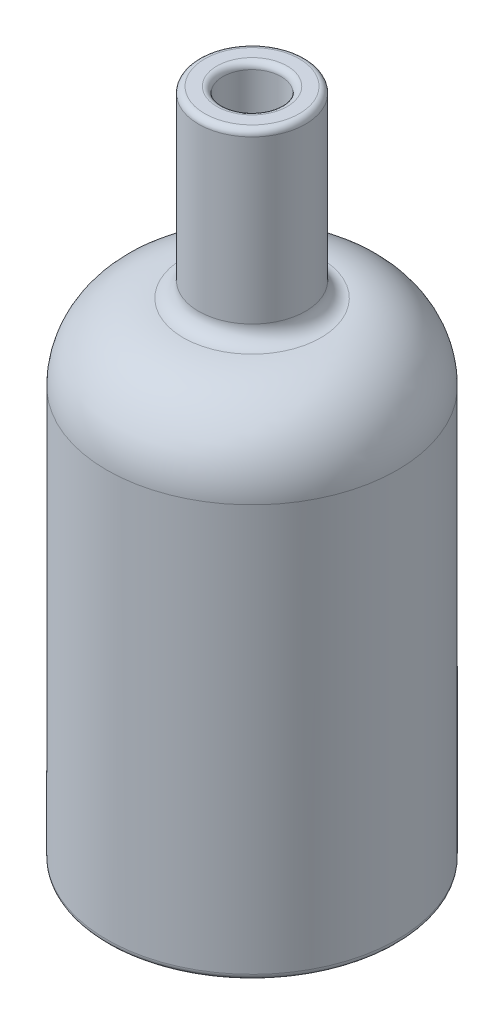
SolidWorks part; units mm, degrees
ref_plane "Front Plane" through (0, 0, 0) normal (0, 0, 1) x (1, 0, 0)
ref_plane "Top Plane" through (0, 0, 0) normal (0, 1, 0) x (1, 0, 0)
ref_plane "Right Plane" through (0, 0, 0) normal (1, 0, 0) x (0, 0, -1)
sketch "Sketch2" plane through (0, 0, 0) normal (0, 0, 1) x (1, 0, 0)
  line L0 (0, 0) -> (0, 75.6247) construction
  line L1 (0, 0) -> (47.5, 0)
  line L2 (47.5, 0) -> (47.5, 160)
  line L3 (47.5, 160) -> (17.5, 160)
  line L4 (17.5, 160) -> (17.5, 220)
  line L5 (0, 8) -> (39.5, 8)
  line L6 (39.5, 8) -> (39.5, 152)
  line L7 (39.5, 152) -> (9.5, 152)
  line L8 (9.5, 152) -> (9.5, 220)
  line L9 (0, 8) -> (0, 0)
  line L10 (9.5, 220) -> (17.5, 220)
  dimension "D1" = 47.5
  dimension "D2" = 160
  dimension "D3" = 60
  dimension "D4" = 17.5
  dimension "D5" = 8
revolve "Revolve1" add sketch "Sketch2" angle 360 about L0
fillet "Fillet1" radius 25 1 edges at (0, 160, -47.5)
fillet "Fillet2" radius 5 1 edges at (0, 160, -17.5)
fillet "Fillet3" radius 2 1 edges at (0, 220, -17.5)
fillet "Fillet4" radius 2 1 edges at (0, 0, -47.5)
fillet "Fillet5" radius 17 1 edges at (0, 152, -39.5)
fillet "Fillet6" radius 2 1 edges at (0, 8, -39.5)
fillet "Fillet7" radius 2 1 edges at (0, 220, -9.5)
